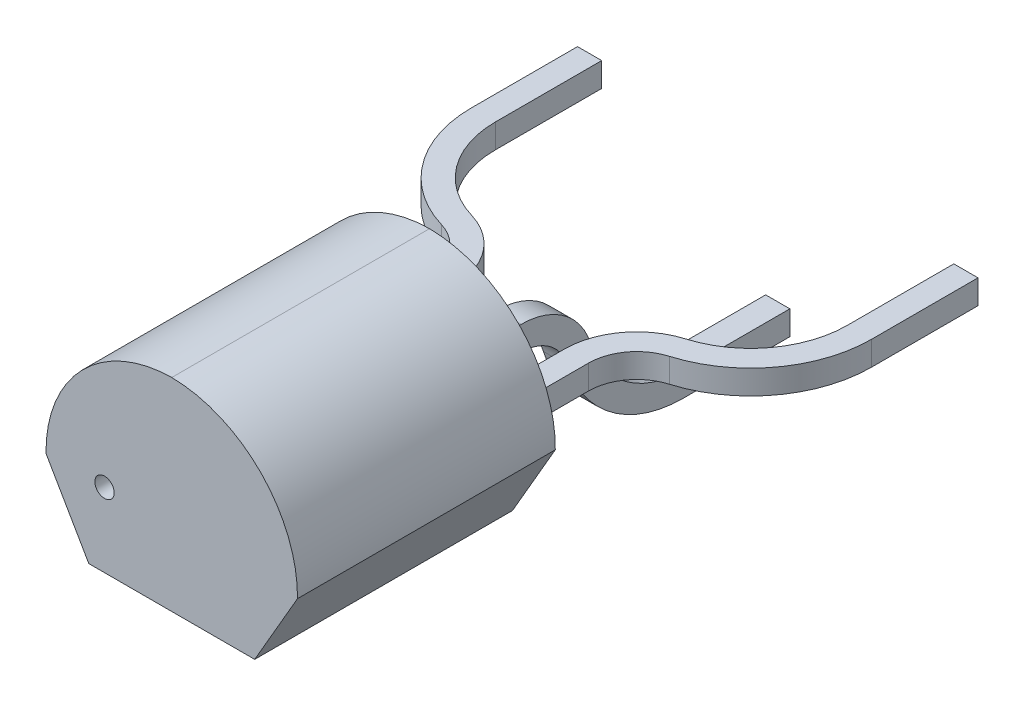
SolidWorks part; units mm, degrees
ref_plane "Спереди" through (0, 0, 0) normal (0, 0, 1) x (1, 0, 0)
ref_plane "Сверху" through (0, 0, 0) normal (0, 1, 0) x (1, 0, 0)
ref_plane "Справа" through (0, 0, 0) normal (1, 0, 0) x (0, 0, -1)
sketch "Эскиз1" plane through (0, 0, 0) normal (0, 0, 1) x (1, 0, 0)
  line L0 (1.14, 0.25) -> (1.64, 0.25)
  line L1 (-0.25, 0.25) -> (0.25, 0.25)
  line L2 (-0.25, 0.25) -> (-0.25, -0.25)
  line L3 (-0.25, -0.25) -> (0.25, -0.25)
  line L4 (0.25, 0.25) -> (0.25, -0.25)
  line L5 (1.14, 0.25) -> (1.14, -0.25)
  line L6 (1.14, -0.25) -> (1.64, -0.25)
  line L7 (1.64, 0.25) -> (1.64, -0.25)
  line L8 (2.53, 0.25) -> (3.03, 0.25)
  line L9 (2.53, 0.25) -> (2.53, -0.25)
  line L10 (2.53, -0.25) -> (3.03, -0.25)
  line L11 (3.03, 0.25) -> (3.03, -0.25)
  line L12 (1.39, 0.25) -> (1.39, -1.8309) construction
  dimension "D1" = 0.5
  dimension "D2" = 0.5
  dimension "D3" = 1.39
ref_plane "Плоскость1" through (0, 0, 2.54) normal (0, 0, 1) x (1, 0, 0)
sketch "Эскиз3" plane through (0, 0, 2.54) normal (0, 0, 1) x (1, 0, 0)
  line L0 (-0.325, -1.53) -> (3.105, -1.53)
  line L6 (-1.21, 0) -> (-0.325, -1.53)
  line L7 (3.99, 0) -> (3.105, -1.53)
  arc A0 (-1.21, 0) -> (1.39, 2.66) centre (1.42, 0.03) cw
  arc A1 (1.39, 2.66) -> (3.99, 0) centre (1.36, 0.03) cw
  dimension "D3" = 2.6302
  dimension "D4" = 2.6302
  dimension "D1" = 5.2
  dimension "D2" = 4.19
  dimension "D5" = 3.43
  dimension "D6" = 1.21
  dimension "D7" = 120.046
extrude "Вытянуть1" add sketch "Эскиз3" along normal blind 5.33
extrude "Вытянуть2" add sketch "Эскиз1" along normal blind 2.54
extrude "Вытянуть3" add sketch "Эскиз1<2>" against normal blind 10.16
sketch "Эскиз1<2>" plane through (0, 0, 0) normal (0, 0, 1) x (1, 0, 0) same geometry as "Эскиз1"
sketch "Эскиз4" plane through (0, 0, 7.87) normal (0, 0, 1) x (1, 0, 0)
  circle A0 centre (0, 0) radius 0.2
extrude "Вырез-Вытянуть1" cut sketch "Эскиз4" against normal blind 0.5
sketch "Эскиз5" plane through (0, -0.25, 0) normal (0, 1, 0) x (1, 0, 0)
  line L0 (1.14, -0.04) -> (1.64, -0.04)
  line L4 (1.64, -2.54) -> (1.64, 10.16)
  line L5 (1.64, 10.16) -> (1.14, 10.16)
  line L6 (1.14, 10.16) -> (1.14, -2.54)
  line L7 (1.14, -2.54) -> (1.64, -2.54)
  line L8 (1.64, -0.04) -> (1.64, 10.16)
  line L9 (1.64, 10.16) -> (1.14, 10.16)
  line L10 (1.14, 10.16) -> (1.14, -0.04)
  dimension "D1" = 0
extrude "Вытянуть4" add sketch "Эскиз5" against normal blind 2.5
sketch "Эскиз6" plane through (-0.25, 0, 0) normal (-1, 0, 0) x (0, 0, 1)
  line L0 (0.04, -0.25) -> (0.04, 0.25)
  line L4 (2.54, 0.25) -> (-10.16, 0.25)
  line L5 (-10.16, 0.25) -> (-10.16, -0.25)
  line L6 (-10.16, -0.25) -> (2.54, -0.25)
  line L7 (2.54, -0.25) -> (2.54, 0.25)
  line L8 (0.04, 0.25) -> (-10.16, 0.25)
  line L9 (-10.16, 0.25) -> (-10.16, -0.25)
  line L10 (-10.16, -0.25) -> (0.04, -0.25)
  dimension "D1" = 0
extrude "Вытянуть5" add sketch "Эскиз6" along normal blind 2.5
sketch "Эскиз7" plane through (3.03, 0, 0) normal (1, 0, 0) x (0, 0, -1)
  line L4 (10.16, -0.25) -> (10.16, 0.25)
  line L5 (-0.04, -0.25) -> (10.16, -0.25)
  line L6 (-0.04, 0.25) -> (-0.04, -0.25)
  line L7 (10.16, 0.25) -> (-0.04, 0.25)
  line L8 (10.16, -0.25) -> (10.16, 0.25)
  line L9 (-0.04, -0.25) -> (10.16, -0.25)
  line L10 (-0.04, 0.25) -> (-0.04, -0.25)
  line L11 (10.16, 0.25) -> (-0.04, 0.25)
  dimension "D1" = 0
extrude "Вытянуть6" add sketch "Эскиз7" along normal blind 2.5
fillet "Скругление1" radius 2.5 3 edges at (5.53, 0, 0.04) (-2.75, 0, 0.04) (1.39, -2.75, 0.04)
fillet "Скругление2" radius 1 3 edges at (3.03, 0, 0.04) (1.39, -0.25, 0.04) (-0.25, 0, 0.04)
sketch "Эскиз9" plane through (0, -0.25, 0) normal (0, -1, 0) x (1, 0, 0)
  line L3 (0.25, 2.54) -> (0.25, -10.16) construction
  line L4 (-2.25, -10.16) -> (-2.25, -2.46)
  line L5 (-2.25, -10.16) -> (-2.25, -2.46)
  line L6 (0.25, 0.8941) -> (0.25, -10.16)
  line L7 (-2.75, -10.16) -> (0.25, -10.16) construction
  line L8 (-2.25, -10.16) -> (0.25, -10.16)
  line L9 (1.39, -10.16) -> (1.39, -5.1788) construction
  line L10 (1.64, -10.16) -> (1.14, -10.16) construction
  line L11 (1.14, -10.16) -> (1.14, -2.46) construction
  line L12 (1.64, -2.46) -> (1.64, -10.16) construction
  line L13 (5.03, -10.16) -> (2.53, -10.16)
  line L14 (2.53, 0.8941) -> (2.53, -10.16)
  line L15 (5.03, -10.16) -> (5.03, -2.46)
  arc A3 (3.6014, -0.5434) -> (5.03, -2.46) centre (3.03, -2.46) cw
  arc A4 (3.6014, -0.5434) -> (2.53, 0.8941) centre (4.03, 0.8941) cw
  arc A5 (-0.8214, -0.5434) -> (0.25, 0.8941) centre (-1.25, 0.8941) ccw
  arc A6 (-0.8214, -0.5434) -> (-2.25, -2.46) centre (-0.25, -2.46) ccw
  arc A7 (-0.8214, -0.5434) -> (0.25, 0.8941) centre (-1.25, 0.8941) ccw
  arc A8 (-0.8214, -0.5434) -> (-2.25, -2.46) centre (-0.25, -2.46) ccw
  dimension "D1" = 0.5
extrude "Вырез-Вытянуть2" cut sketch "Эскиз9" against normal blind 2.5
sketch "Эскиз10" plane through (1.14, 0, 0) normal (-1, 0, 0) x (0, 0, 1)
  line L3 (-10.16, 0.25) -> (-10.16, -2.75) construction
  line L4 (-2.46, -2.25) -> (-10.16, -2.25)
  line L5 (-2.46, -2.25) -> (-10.16, -2.25)
  line L6 (-10.16, 0.25) -> (-10.16, -2.25)
  line L7 (2.54, 0.25) -> (-10.16, 0.25) construction
  line L8 (0.8941, 0.25) -> (-10.16, 0.25)
  arc A5 (0.8941, 0.25) -> (-0.5434, -0.8214) centre (0.8941, -1.25) ccw
  arc A6 (-2.46, -2.25) -> (-0.5434, -0.8214) centre (-2.46, -0.25) ccw
  arc A7 (0.8941, 0.25) -> (-0.5434, -0.8214) centre (0.8941, -1.25) ccw
  arc A8 (-2.46, -2.25) -> (-0.5434, -0.8214) centre (-2.46, -0.25) ccw
  dimension "D1" = 0.5
extrude "Вырез-Вытянуть3" cut sketch "Эскиз10" against normal blind 1
sketch "Эскиз11" plane through (0, 0, -10.16) normal (0, 0, -1) x (-1, 0, 0)
  line L1 (-6.119, -4.9501) -> (3.9427, -4.9501)
  line L2 (-6.119, -4.9501) -> (-6.119, 1.6571)
  line L3 (-6.119, 1.6571) -> (3.9427, 1.6571)
  line L4 (3.9427, -4.9501) -> (3.9427, 1.6571)
extrude "Вырез-Вытянуть4" cut sketch "Эскиз11" against normal blind 5.5
sketch "Эскиз12" plane through (0, 0, -4.66) normal (0, 0, -1) x (-1, 0, 0)
  line L0 (-1.39, -2.5) -> (-1.39, -2.0107) construction
  line L1 (-1.39, -2.0107) -> (-1.39, -2.5) construction
  line L2 (-1.39, -2.5) -> (-0.7741, -2.5) construction
  line L3 (-1.64, -2.25) -> (-1.14, -2.25) construction
  line L4 (-1.14, -2.75) -> (-1.64, -2.75) construction
  line L5 (-1.64, -2.75) -> (-1.64, -2.25) construction
  line L6 (-1.14, -2.25) -> (-1.14, -2.75) construction
  circle A0 centre (-1.39, -2.5) radius 0.1565
extrude "Вырез-Вытянуть5" cut sketch "Эскиз12" against normal blind 1
